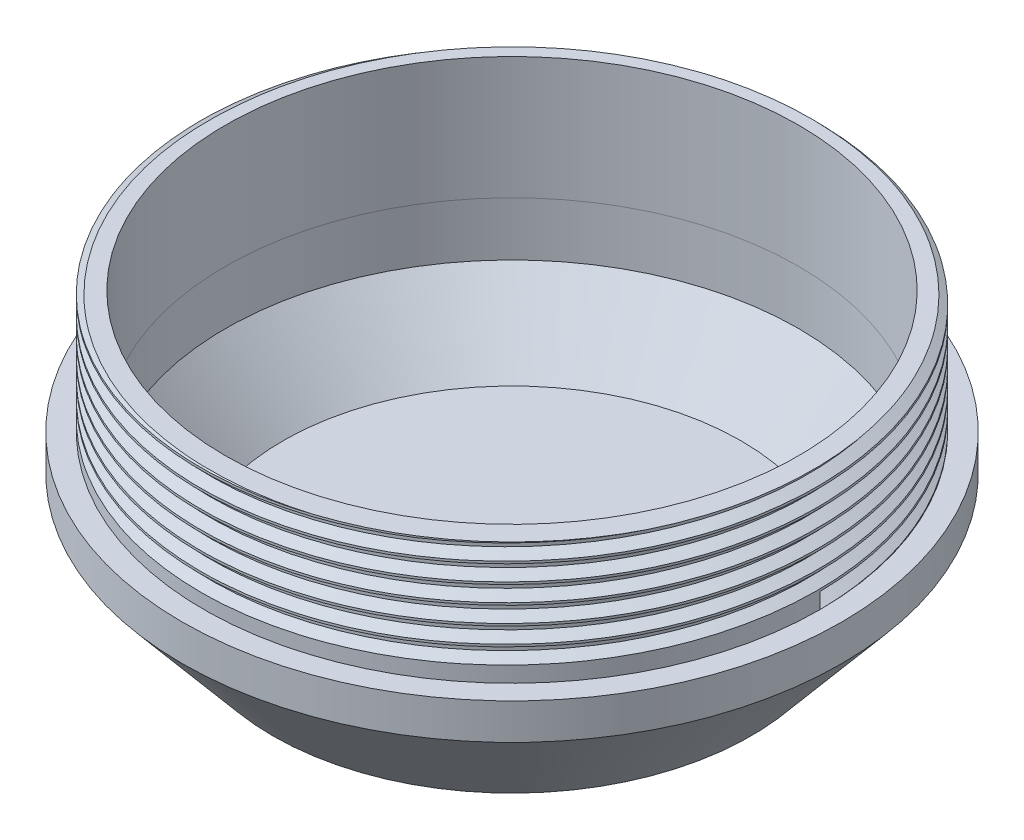
SolidWorks part; units mm, degrees
ref_plane "Alzado" through (0, 0, 0) normal (0, 0, 1) x (1, 0, 0)
ref_plane "Planta" through (0, 0, 0) normal (0, 1, 0) x (1, 0, 0)
ref_plane "Vista lateral" through (0, 0, 0) normal (1, 0, 0) x (0, 0, -1)
sketch "Croquis5" plane through (0, 0, 0) normal (0, 0, 1) x (1, 0, 0)
  line L1 (0, 0) -> (33.22, 0)
  line L2 (33.22, 0) -> (45.8065, 15)
  line L3 (45.8065, 15) -> (45.8065, 40)
  line L4 (45.8065, 40) -> (0, 40)
  line L6 (45.8065, 15) -> (45.8065, 0) construction
  line L7 (45.8065, 0) -> (33.22, 0) construction
  line L8 (0, 0) -> (0, 3)
  line L9 (0, 3) -> (31.8211, 3)
  line L10 (31.8211, 3) -> (39.8065, 12.5166)
  line L11 (39.8065, 12.5166) -> (39.8065, 37)
  line L12 (39.8065, 37) -> (0, 37)
  line L13 (0, 37) -> (0, 40)
  line L14 (0, 0) -> (0, 65.0712) construction
  dimension "D1" = 40
  dimension "D2" = 50
  dimension "D3" = 15
  dimension "D4" = 33.22
  dimension "D5" = 3
  dimension "D6" = 6
  dimension "D7" = 3
  dimension "D8" = 3
revolve "Revolución2" add sketch "Croquis5" angle 360 about L14
sketch "Croquis7" plane through (0, 40, 0) normal (0, 1, 0) x (1, 0, 0)
  line L5 (-25, 25) -> (25, 25)
  line L6 (-25, 25) -> (-25, -25)
  line L7 (-25, -25) -> (25, -25)
  line L8 (25, 25) -> (25, -25)
  line L9 (-25, 25) -> (25, -25) construction
  line L10 (-25, -25) -> (25, 25) construction
  point P0 (0, 0)
  dimension "D1" = 50
  dimension "D2" = 50
extrude "Saliente-Extruir3" add sketch "Croquis7" along normal blind 100
sketch "Croquis10" plane through (0, 0, 25) normal (0, 0, 1) x (1, 0, 0)
  line L0 (-25, 40) -> (-7.3673, 140)
  line L1 (-25, 140) -> (25, 140) construction
  line L2 (-7.3673, 140) -> (-25, 140)
  line L3 (-25, 140) -> (-25, 40)
  line L4 (25, 40) -> (25, 140)
  line L5 (25, 140) -> (7.3673, 140)
  line L6 (7.3673, 140) -> (25, 40)
  dimension "D1" = 10
  dimension "D2" = 10
extrude "Cortar-Extruir6" cut sketch "Croquis10" against normal through all
sketch "Croquis11" plane through (0, 0, 0) normal (1, 0, 0) x (0, 0, -1)
  line L0 (-25, 40) -> (-7.3673, 140)
  line L1 (25, 140) -> (-25, 140) construction
  line L2 (-7.3673, 140) -> (-25, 140)
  line L3 (-25, 140) -> (-25, 40)
  line L4 (25, 40) -> (25, 140)
  line L5 (25, 140) -> (7.3673, 140)
  line L6 (7.3673, 140) -> (25, 40)
  dimension "D1" = 10
  dimension "D2" = 10
extrude "Cortar-Extruir7" cut sketch "Croquis11" against normal through all both and the other way through all
sketch "Croquis12" plane through (0, 0, 0) normal (0, 0, 1) x (1, 0, 0)
  line L0 (-19.9229, 40) -> (19.9229, 40)
  line L1 (-25, 40) -> (25, 40) construction
  line L2 (19.9229, 40) -> (2.2902, 140)
  line L3 (2.2902, 140) -> (-2.2902, 140)
  line L4 (-2.2902, 140) -> (-19.9229, 40)
  line L7 (-25, 40) -> (-7.3673, 140) construction
  line L8 (7.3673, 140) -> (25, 40) construction
  dimension "D1" = 5
  dimension "D2" = 5
  dimension "D3" = 100
extrude "Cortar-Extruir8" cut sketch "Croquis12" against normal through all both and the other way through all
sketch "Croquis13" plane through (0, 0, 0) normal (1, 0, 0) x (0, 0, -1)
  line L0 (-19.9229, 40) -> (19.9229, 40)
  line L1 (-25, 40) -> (25, 40) construction
  line L2 (19.9229, 40) -> (2.2902, 140)
  line L3 (2.2902, 140) -> (-2.2902, 140)
  line L4 (-2.2902, 140) -> (-19.9229, 40)
  line L5 (-7.3673, 140) -> (-25, 40) construction
  line L6 (25, 40) -> (7.3673, 140) construction
  dimension "D1" = 5
  dimension "D2" = 5
  dimension "D3" = 100
extrude "Cortar-Extruir9" cut sketch "Croquis13" against normal through all both and the other way through all
fillet "Redondeo1" radius 2.5 16 edges at (-11.1065, 90, -11.1065) (-11.1065, 90, -16.1837) (-16.1837, 90, -16.1837) (-16.1837, 90, -11.1065) (11.1065, 90, -11.1065) (16.1837, 90, -11.1065) (16.1837, 90, -16.1837) (11.1065, 90, -16.1837) (11.1065, 90, 11.1065) (11.1065, 90, 16.1837) (16.1837, 90, 16.1837) (16.1837, 90, 11.1065) (-11.1065, 90, 11.1065) (-11.1065, 90, 16.1837) (-16.1837, 90, 11.1065) (-16.1837, 90, 16.1837)
sketch "Croquis14" plane through (0, 140, 0) normal (0, 1, 0) x (1, 0, 0)
  line L5 (-12.5, 12.5) -> (12.5, 12.5)
  line L6 (-12.5, 12.5) -> (-12.5, -12.5)
  line L7 (-12.5, -12.5) -> (12.5, -12.5)
  line L8 (12.5, 12.5) -> (12.5, -12.5)
  line L9 (-12.5, 12.5) -> (12.5, -12.5) construction
  line L10 (-12.5, -12.5) -> (12.5, 12.5) construction
  point P0 (0, 0)
  dimension "D1" = 25
  dimension "D2" = 25
extrude "Saliente-Extruir4" add sketch "Croquis14" along normal blind 5
sketch "Croquis15" plane through (0, 0, 0) normal (0, 0, 1) x (1, 0, 0)
  line L0 (45.8065, 40) -> (-45.8065, 40) construction
  line L1 (-52.7788, 165.5779) -> (51.692, 165.5779)
  line L2 (-52.7788, 165.5779) -> (-52.7788, 20)
  line L3 (-52.7788, 20) -> (51.692, 20)
  line L4 (51.692, 165.5779) -> (51.692, 20)
  dimension "D1" = 20
extrude "Cortar-Extruir10" cut sketch "Croquis15" against normal through all both and the other way through all
sketch "Croquis16" plane through (0, 20, 0) normal (0, 1, 0) x (1, 0, 0)
  circle A0 centre (0, 0) radius 42.8065
  circle A1 centre (0, 0) radius 39.8065
  circle A2 centre (0, 0) radius 45.8065 construction
  dimension "D1" = 3
  dimension "D2" = 3
extrude "Saliente-Extruir5" add sketch "Croquis16" along normal blind 17 separate body
thread "Rosca2" pitch 2.5 method cut profile "Perfil de rosca4" start angle 0, offset 0, length 17, pitch 2.5, diameter 85.613
ref_plane "Plano4" through (42.8065, 20, 0) normal (0, 0, 1) x (1, 0, 0)
sketch "Perfil de rosca4" plane through (42.8065, 20, 0) normal (0, 0, 1) x (1, 0, 0)
  line L0 (0, 0) -> (0, 2.5) construction
  line L11 (0, 0) -> (0, 2.1875)
  line L12 (0, 2.1875) -> (-1.3532, 1.4062)
  line L13 (-1.3532, 1.4062) -> (-1.3532, 0.7812)
  line L15 (-1.3532, 0.7812) -> (0, 0)
  line L17 (-1.3532, 1.0937) -> (0, 1.0937) construction
  point P2 (0, 0)
  dimension "Pitch" = 2.5
  dimension "Profile_Angle" = 60
  dimension "Profile_Land" = 0.625
  dimension "Profile_Height" = 1.3532
